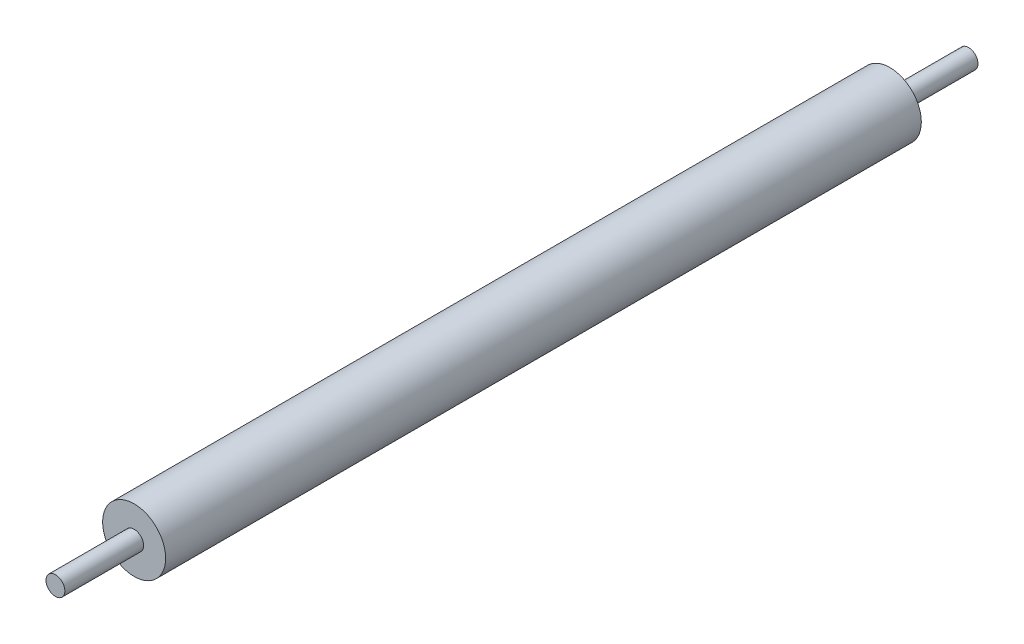
SolidWorks part; units mm, degrees
material "AISI 1010 Steel, hot rolled bar"
ref_plane "Front Plane" through (0, 0, 0) normal (0, 0, 1) x (1, 0, 0)
ref_plane "Top Plane" through (0, 0, 0) normal (0, 1, 0) x (1, 0, 0)
ref_plane "Right Plane" through (0, 0, 0) normal (1, 0, 0) x (0, 0, -1)
sketch "Sketch1" plane through (0, 0, 0) normal (0, 0, 1) x (1, 0, 0)
  circle A0 centre (0, 0) radius 50
  dimension "D1" = 100
extrude "Boss-Extrude1" add sketch "Sketch1" along normal mid plane 1200
sketch "Sketch4" plane through (0, 0, 0) normal (0, 0, 1) x (1, 0, 0)
  line L1 (-5, 14.1421) -> (-5, 18.3)
  line L4 (5, 18.3) -> (5, 14.1421)
  line L5 (-5, 18.3) -> (5, 18.3)
  arc A2 (-5, 14.1421) -> (5, 14.1421) centre (0, 0) ccw
  dimension "D2" = 10
  dimension "D1" = 15
  dimension "D3" = 18.3
  dimension "D4" = 5
extrude "Boss-Extrude2" add sketch "Sketch4" along normal mid plane 1200 contours L1 A2 L4 L5 region at (0, 0.7959, 0)
sketch "Sketch5" [suppressed] plane through (0, 0, 0) normal (0, 0, 1) x (1, 0, 0)
  line L0 (7, 7.1414) -> (7, -7.1414) construction
  line L1 (-7, 7.1414) -> (-7, -7.1414) construction
  line L2 (7, 7.1414) -> (7, -7.1414)
  line L3 (-7, 7.1414) -> (-7, -7.1414)
  line L7 (-5, 18.3) -> (-5, 14.1421)
  line L8 (-5, 18.3) -> (-5, 14.1421)
  line L9 (5, 18.3) -> (-5, 18.3)
  line L10 (5, 18.3) -> (-5, 18.3)
  line L11 (5, 14.1421) -> (5, 18.3)
  line L12 (5, 14.1421) -> (5, 18.3)
  arc A1 (-5, 14.1421) -> (5, 14.1421) centre (0, 0) ccw
  arc A3 (-5, 14.1421) -> (5, 14.1421) centre (0, 0) ccw
  dimension "D1" = 0
extrude "Boss-Extrude3" [suppressed] add sketch "Sketch5" along normal mid plane 1210
ref_axis "Axis1" through (0, 0, 600) along (0, 0, -1)
sketch "Sketch6" plane through (0, 0, 0) normal (0, 0, 1) x (1, 0, 0)
  circle A0 centre (0, 0) radius 15
  dimension "D1" = 30
extrude "Boss-Extrude4" add sketch "Sketch6" along normal blind 125 from offset 600
mirror "Mirror1" about plane through (0, 0, 0) normal (0, 0, 1) of "Boss-Extrude4"
ref_axis "Axis2" through (0, 0, 600) along (0, 0, -1)
